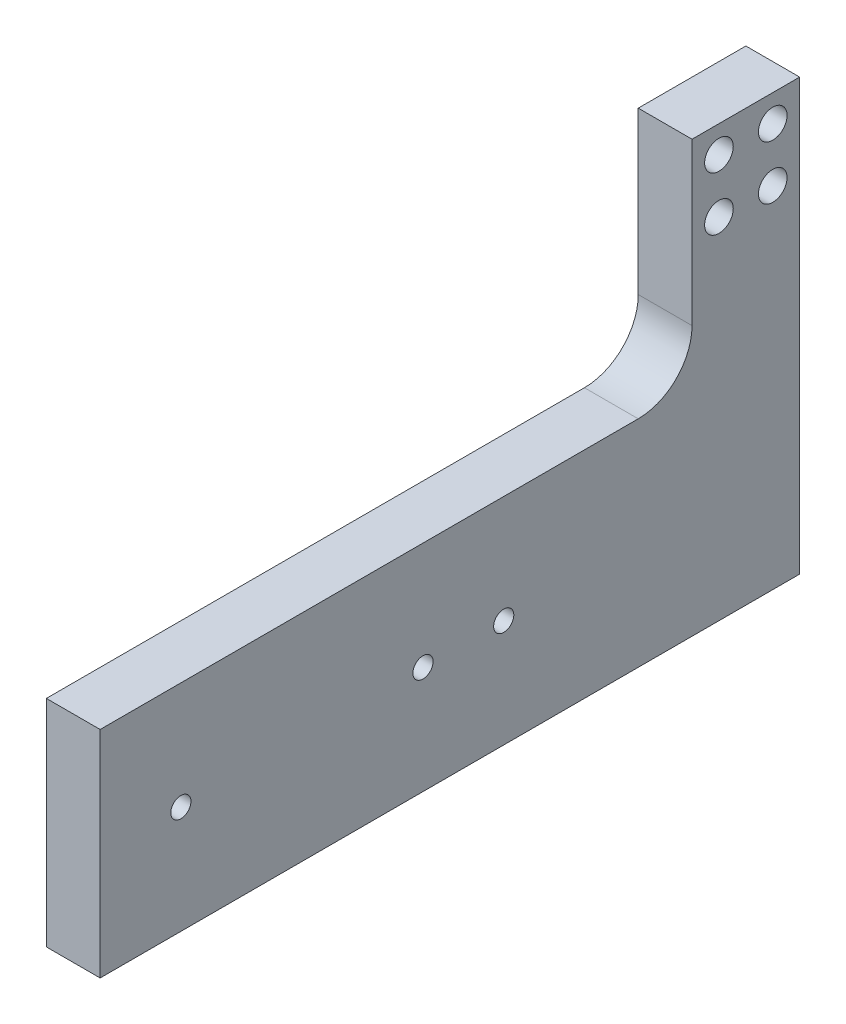
SolidWorks part; units mm, degrees
material "6061-T6 (SS)"
ref_plane "Front Plane" through (0, 0, 0) normal (0, 0, 1) x (1, 0, 0)
ref_plane "Top Plane" through (0, 0, 0) normal (0, 1, 0) x (1, 0, 0)
ref_plane "Right Plane" through (0, 0, 0) normal (1, 0, 0) x (0, 0, -1)
sketch "Sketch1" plane through (0, 0, 0) normal (1, 0, 0) x (0, 0, -1)
  line L0 (0, 0) -> (0, 101.6)
  line L1 (0, 101.6) -> (-25.4, 101.6)
  line L2 (-25.4, 101.6) -> (-25.4, 50.8)
  line L3 (-25.4, 50.8) -> (-165.1, 50.8)
  line L4 (-165.1, 50.8) -> (-165.1, 0)
  line L5 (-165.1, 0) -> (0, 0)
  line L6 (-69.85, 25.4) -> (-146.05, 25.4) construction
  circle A0 centre (-146.05, 25.4) radius 2.3813
  circle A1 centre (-88.9, 25.4) radius 2.3813
  circle A2 centre (-69.85, 25.4) radius 2.3813
  dimension "D5" = 4.7625
  dimension "D1" = 101.6
  dimension "D2" = 165.1
  dimension "D3" = 50.8
  dimension "D4" = 25.4
  dimension "D6" = 19.05
  dimension "D7" = 76.2
  dimension "D8" = 95.25
  dimension "D9" = 25.4
extrude "Boss-Extrude1" add sketch "Sketch1" along normal blind 12.7
hole_wizard "1/4 Clearance Hole1" positions "Sketch2" profile "Sketch3" hole size "1/4" standard "ANSI Inch" end condition through all
sketch "Sketch2" plane through (12.7, 0, 0) normal (1, 0, 0) x (0, 0, -1)
  line L0 (-25.4, 101.6) -> (-25.4, 50.8) construction
  line L1 (0, 0) -> (0, 101.6) construction
  point P0 (-19.05, 95.25)
  point P2 (-6.35, 95.25)
  point P4 (-6.35, 82.55)
  point P6 (-19.05, 82.55)
  dimension "D1" = 6.35
  dimension "D2" = 6.35
  dimension "D3" = 6.35
  dimension "D4" = 6.35
  dimension "D5" = 12.7
  dimension "D6" = 12.7
  dimension "D7" = 6.35
  dimension "D8" = 6.35
sketch "Sketch3" plane through (12.7, 95.25, 19.05) normal (0, 1, 0) x (0, 0, -1)
  line L0 (0, 0) -> (0, 12.7)
  line L1 (0, 12.7) -> (3.3782, 12.7)
  line L2 (3.3782, 12.7) -> (3.3782, 0)
  line L5 (3.3782, 0) -> (0, 0)
  line L11 (0, -6.35) -> (0, 107.95) construction
  dimension "Thru Hole Dia." = 6.7564
  dimension "Thru Hole Depth" = 12.7
ref_point "Point1"
ref_point "Point2"
ref_point "Point3"
fillet "Fillet1" radius 12.7 1 edges at (6.35, 50.8, 25.4)
